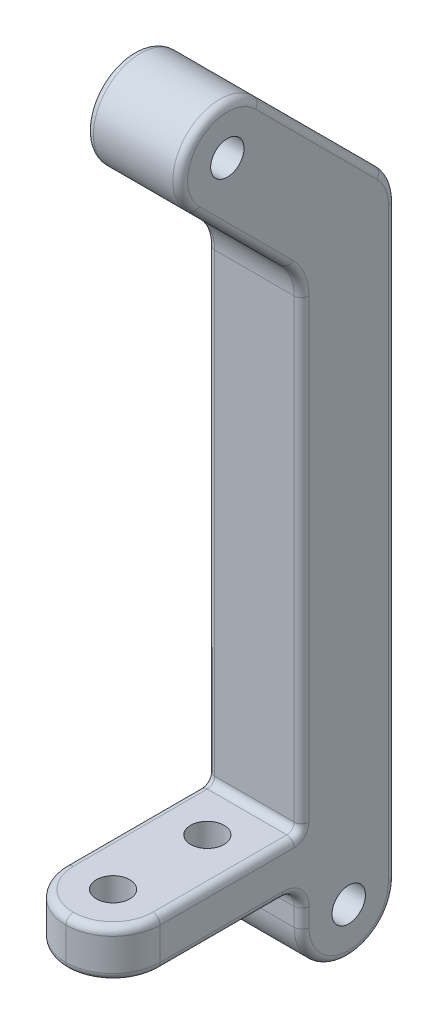
SolidWorks part; units mm, degrees
ref_plane "Front Plane" through (0, 0, 0) normal (0, 0, 1) x (1, 0, 0)
ref_plane "Top Plane" through (0, 0, 0) normal (0, 1, 0) x (1, 0, 0)
ref_plane "Right Plane" through (0, 0, 0) normal (1, 0, 0) x (0, 0, -1)
sketch "Sketch1" plane through (0, 0, 0) normal (1, 0, 0) x (0, 0, -1)
  line L0 (-6.35, 11.3) -> (-31.75, 11.3)
  line L1 (-31.75, 11.3) -> (-31.75, 4.95)
  line L2 (-31.75, 4.95) -> (-6.35, 4.95)
  line L3 (-6.35, 4.95) -> (-6.35, -6.35)
  line L4 (-6.35, -6.35) -> (6.35, -6.35)
  line L5 (6.35, -6.35) -> (6.35, 11.3)
  line L6 (-6.35, 11.3) -> (-6.35, 76.3197)
  line L7 (-6.35, 76.3197) -> (-20.8401, 90.8099)
  line L8 (-11.8599, 99.7901) -> (6.35, 81.5803)
  line L9 (6.35, 81.5803) -> (6.35, 11.3)
  circle A0 centre (0, 0) radius 2.25
  circle A2 centre (-16.35, 95.3) radius 2.25
  circle A3 centre (-16.35, 95.3) radius 6.35
  dimension "D1" = 4.5
  dimension "D3" = 6.35
  dimension "D6" = 6.35
  dimension "D8" = 4.5
  dimension "D10" = 12.7
  dimension "D2" = 11.3
  dimension "D4" = 31.75
  dimension "D5" = 6.35
  dimension "D7" = 6.35
  dimension "D9" = 84
  dimension "D11" = 10
  dimension "D12" = 135
extrude "Boss-Extrude1" add sketch "Sketch1" along normal blind 12.7 contours A3 L7 L6 L0 L1 L2 L3 L4 L5 L9 L8 A0 | A3 A2 region at (0, 41.3692, 3.0344) region at (0, 99.6631, 20.7131)
fillet "Fillet1" radius 6.35 4 edges at (6.35, 81.5803, -6.35) (6.35, 76.3197, 6.35) (6.35, -6.35, -6.35) (6.35, -6.35, 6.35)
fillet "Fillet3" radius 6.35 2 edges at (0, 8.125, 31.75) (12.7, 8.125, 31.75)
fillet "Fillet5" radius 2.5 1 edges at (6.35, 4.95, 6.35)
fillet "Fillet4" radius 1 31 edges at (10.8401, 11.3, 29.8901) (1.8599, 11.3, 29.8901) (12.7, 11.3, 15.875) (0, 11.3, 15.875) (12.7, 42.4947, 6.35) (0, 42.4947, 6.35) (12.7, 76.1195, 6.8334) (0, 76.1195, 6.8334) (12.7, 84.4947, 14.525) (0, 84.4947, 14.525) (12.7, 99.7901, 20.8401) (0, 99.7901, 20.8401) (12.7, 91.6151, 3.6849) (0, 91.6151, 3.6849) (12.7, 81.38, -5.8666) (0, 81.38, -5.8666) (12.7, 39.475, -6.35) (0, 39.475, -6.35) (12.7, -4.4901, -4.4901) (0, -4.4901, -4.4901) (12.7, -4.4901, 4.4901) (0, -4.4901, 4.4901) (12.7, 1.225, 6.35) (0, 1.225, 6.35) (12.7, 4.95, 17.125) (10.8401, 4.95, 29.8901) (1.8599, 4.95, 29.8901) (0, 4.95, 17.125) (6.35, 11.3, 6.35) (12.7, 4.2178, 7.0822) (0, 4.2178, 7.0822)
sketch "Sketch2" plane through (0, 4.95, 0) normal (0, -1, 0) x (1, 0, 0)
  line L1 (0, 8.85) -> (0, 25.4) construction
  circle A0 centre (6.35, 12.7) radius 2.25
  circle A1 centre (6.35, 25.4) radius 2.25
  point P8 (0, 0)
  point P10 (6.8825, 13.1514)
  dimension "D1" = 4.5
  dimension "D2" = 12.7
  dimension "D3" = 12.7
  dimension "D4" = 6.35
extrude "Cut-Extrude1" cut sketch "Sketch2" against normal up to next
